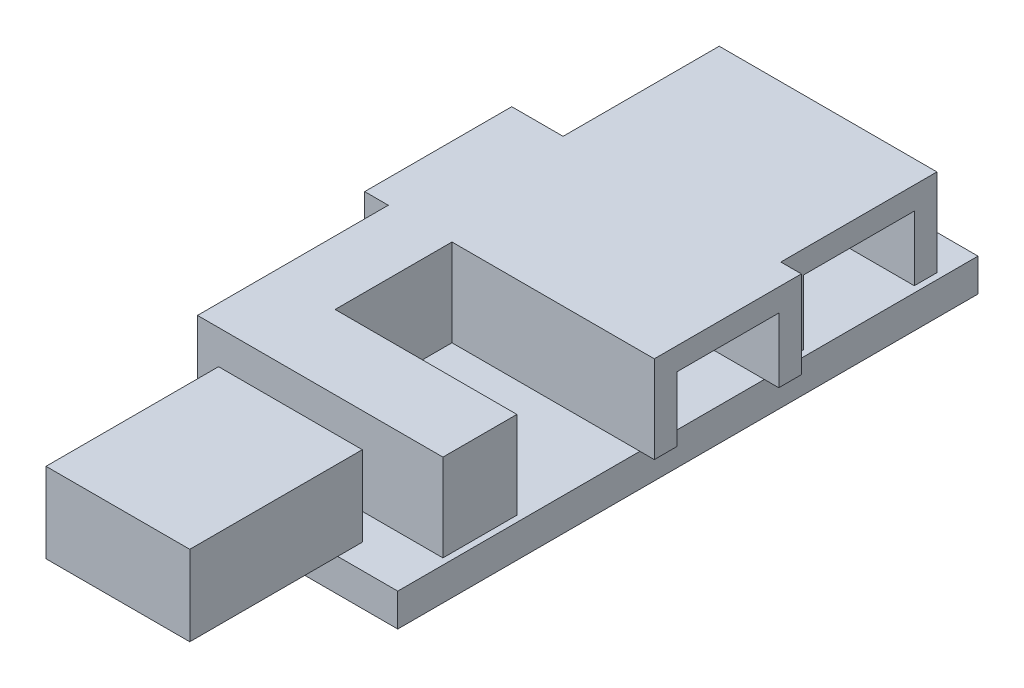
SolidWorks part; units mm, degrees
ref_plane "Front Plane" through (0, 0, 0) normal (0, 0, 1) x (1, 0, 0)
ref_plane "Top Plane" through (0, 0, 0) normal (0, 1, 0) x (1, 0, 0)
ref_plane "Right Plane" through (0, 0, 0) normal (1, 0, 0) x (0, 0, -1)
sketch "Sketch1" plane through (0, 0, 0) normal (0, 1, 0) x (1, 0, 0)
  line L1 (16.3195, 35.8775) -> (-16.3195, 35.8775)
  line L2 (16.3195, 35.8775) -> (16.3195, -35.8775)
  line L3 (16.3195, -35.8775) -> (-16.3195, -35.8775)
  line L4 (-16.3195, 35.8775) -> (-16.3195, -35.8775)
  line L5 (16.3195, 35.8775) -> (-16.3195, -35.8775) construction
  line L6 (16.3195, -35.8775) -> (-16.3195, 35.8775) construction
  point P0 (0, 0)
  dimension "D1" = 71.755
  dimension "D2" = 32.639
extrude "Boss-Extrude1" add sketch "Sketch1" along normal blind 4.064
sketch "Sketch2" plane through (0, 4.064, 0) normal (0, 1, 0) x (1, 0, 0)
  line L0 (16.3195, 35.8775) -> (-16.3195, 35.8775) construction
  line L1 (-11.3665, 31.5595) -> (15.5575, 31.5595)
  line L2 (-11.3665, 31.5595) -> (-11.3665, 12.2555)
  line L3 (-11.3665, 12.2555) -> (15.5575, 12.2555)
  line L4 (15.5575, 31.5595) -> (15.5575, 12.2555)
  line L5 (16.3195, -35.8775) -> (16.3195, 35.8775) construction
  line L6 (-16.3195, -35.8775) -> (16.3195, -35.8775) construction
  line L7 (18.0975, 12.2555) -> (-17.7165, 12.2555)
  line L8 (18.0975, 12.2555) -> (18.0975, -5.9309)
  line L9 (18.0975, -5.9309) -> (-17.7165, -5.9309)
  line L10 (-17.7165, 12.2555) -> (-17.7165, -5.9309)
  line L11 (-14.7955, -5.9309) -> (-6.9215, -5.9309)
  line L12 (-14.7955, -5.9309) -> (-14.7955, -29.5275)
  line L13 (-14.7955, -29.5275) -> (-6.9215, -29.5275)
  line L14 (-6.9215, -5.9309) -> (-6.9215, -29.5275)
  line L15 (-16.3195, 35.8775) -> (-16.3195, -35.8775) construction
  line L17 (-6.9215, -20.3835) -> (15.5575, -20.3835)
  line L18 (-6.9215, -20.3835) -> (-6.9215, -29.5275)
  line L19 (-6.9215, -29.5275) -> (15.5575, -29.5275)
  line L20 (15.5575, -20.3835) -> (15.5575, -29.5275)
  dimension "D1" = 4.318
  dimension "D2" = 0.762
  dimension "D3" = 19.304
  dimension "D4" = 26.924
  dimension "D5" = 18.1864
  dimension "D6" = 2.54
  dimension "D7" = 35.814
  dimension "D8" = 6.35
  dimension "D9" = 7.874
  dimension "D10" = 1.524
  dimension "D11" = 9.144
  dimension "D12" = 0.762
extrude "Boss-Extrude2" add sketch "Sketch2" along normal blind 10.795 contours L20 L17 L14 L19 | L14 L9 L12 L13 | L4 L1 L2 L3 | L9 L10 L7 L8 region at (2.0955, 4.064, -21.9075) region at (-10.8585, 4.064, 17.7292) region at (4.318, 4.064, 24.9555)
sketch "Sketch3" plane through (0, 4.064, 0) normal (0, 1, 0) x (1, 0, 0)
  line L0 (0, -1000) -> (0, 49000) construction
  line L1 (-8.89, -32.8295) -> (8.89, -32.8295)
  line L2 (-8.89, -32.8295) -> (-8.89, -54.1655)
  line L3 (-8.89, -54.1655) -> (8.89, -54.1655)
  line L4 (8.89, -32.8295) -> (8.89, -54.1655)
  line L5 (-16.3195, -35.8775) -> (16.3195, -35.8775) construction
  point P5 (0, -32.8295)
  dimension "D1" = 17.78
  dimension "D2" = 21.336
  dimension "D3" = 3.048
extrude "Boss-Extrude3" add sketch "Sketch3" along normal blind 9.906
sketch "Sketch4" plane through (15.5575, 0, 0) normal (1, 0, 0) x (0, 0, -1)
  line L9 (15.0495, 12.065) -> (15.0495, 4.064)
  line L10 (28.7655, 12.065) -> (15.0495, 12.065)
  line L11 (28.7655, 4.064) -> (28.7655, 12.065)
  line L12 (15.0495, 12.065) -> (15.0495, 4.064)
  line L13 (28.7655, 12.065) -> (15.0495, 12.065)
  line L14 (28.7655, 4.064) -> (28.7655, 12.065)
  line L18 (15.0495, 4.064) -> (28.7655, 4.064)
  line L19 (9.4615, 4.064) -> (-3.1369, 4.064)
  line L21 (-3.1369, 12.065) -> (-3.1369, 4.064)
  line L22 (9.4615, 12.065) -> (-3.1369, 12.065)
  line L23 (9.4615, 4.064) -> (9.4615, 12.065)
  line L24 (-3.1369, 12.065) -> (-3.1369, 4.064)
  line L25 (9.4615, 12.065) -> (-3.1369, 12.065)
  line L26 (9.4615, 4.064) -> (9.4615, 12.065)
  dimension "D1" = 2.794
  dimension "D2" = 2.794
extrude "Cut-Extrude1" cut sketch "Sketch4" against normal through all and the other way through all
